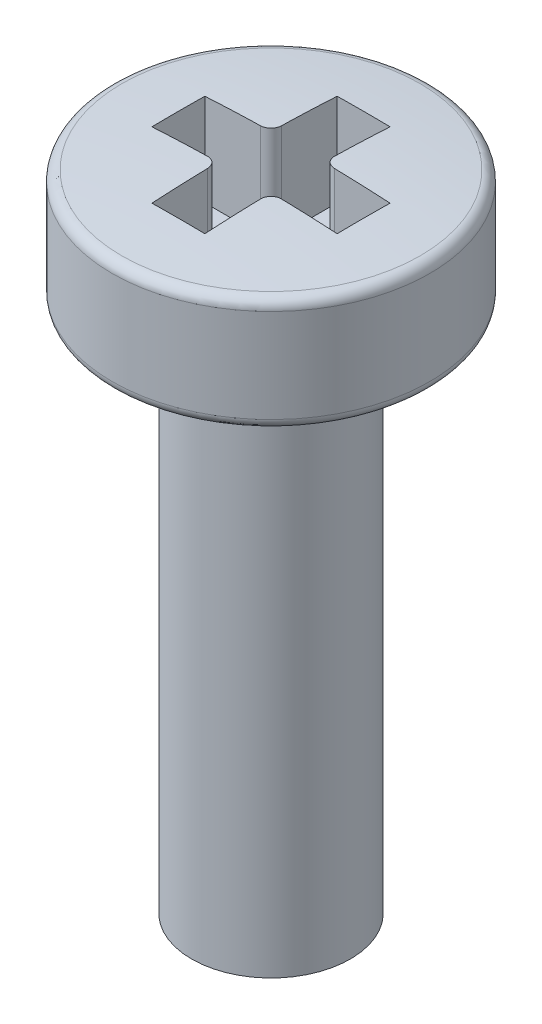
SolidWorks part; units mm, degrees
ref_plane "Alzado" through (0, 0, 0) normal (0, 0, 1) x (1, 0, 0)
ref_plane "Planta" through (0, 0, 0) normal (0, 1, 0) x (1, 0, 0)
ref_plane "Vista lateral" through (0, 0, 0) normal (1, 0, 0) x (0, 0, -1)
sketch "Croquis1" plane through (0, 0, 0) normal (0, 1, 0) x (1, 0, 0)
  circle A0 centre (0, 0) radius 1.5
  dimension "D1" = 3
extrude "Saliente-Extruir1" add sketch "Croquis1" along normal blind 10 contours A0
cosmetic thread "Cosmetic Thread1" parameters "D2"=2.439
ref_plane "Plano1" through (0, 13, 0) normal (0, 1, 0) x (1, 0, 0)
sketch "Croquis4" plane through (0, 0, 0) normal (0, 0, 1) x (1, 0, 0)
  line L0 (1.5, 10) -> (-1.5, 10) construction
  line L1 (0, 10) -> (2.8, 10)
  line L2 (0, 10) -> (0, 12.3)
  line L3 (-1.3027, 12.3) -> (0, 12.3) construction
  line L4 (3, 10.2) -> (3, 11.9682)
  arc A0 (2.8188, 12.1673) -> (0, 12.3) centre (0, -17.7) ccw
  arc A1 (2.8188, 12.1673) -> (3, 11.9682) centre (2.8, 11.9682) cw
  arc A2 (2.8, 10) -> (3, 10.2) centre (2.8, 10.2) ccw
  point P12 (3, 10)
  dimension "D2" = 0.2
  dimension "D4" = 30
  dimension "D1" = 3
  dimension "D3" = 2.3
revolve "Revolución1" add sketch "Croquis4" angle 360 about L2
sketch "Croquis5" plane through (0, 13, 0) normal (0, 1, 0) x (1, 0, 0)
  line L0 (-0.5, -0.7) -> (-0.5, -1.75)
  line L1 (-0.5, 1.75) -> (0.5, 1.75)
  line L2 (-0.5, 1.75) -> (-0.5, 0.7)
  line L3 (-0.5, -1.75) -> (0.5, -1.75)
  line L4 (0.5, 1.75) -> (0.5, 0.7)
  line L5 (1.75, 0.5) -> (0.7, 0.5)
  line L6 (1.75, 0.5) -> (1.75, -0.5)
  line L7 (1.75, -0.5) -> (0.7, -0.5)
  line L8 (-1.75, 0.5) -> (-1.75, -0.5)
  line L9 (-0.7, 0.5) -> (-1.75, 0.5)
  line L10 (0.5, -0.7) -> (0.5, -1.75)
  line L11 (-0.7, -0.5) -> (-1.75, -0.5)
  line L12 (-1.75, 0) -> (1.75, 0) construction
  line L13 (0, 1.75) -> (0, -1.75) construction
  arc A0 (-0.5, -0.7) -> (-0.7, -0.5) centre (-0.7, -0.7) ccw
  arc A1 (0.5, -0.7) -> (0.7, -0.5) centre (0.7, -0.7) cw
  arc A2 (0.7, 0.5) -> (0.5, 0.7) centre (0.7, 0.7) cw
  arc A3 (-0.5, 0.7) -> (-0.7, 0.5) centre (-0.7, 0.7) cw
  point P19 (-0.5, -0.5)
  point P26 (-0.5, 0.5)
  dimension "D2" = 0.2
  dimension "D1" = 1
  dimension "D3" = 3.5
extrude "Cortar-Extruir1" cut sketch "Croquis5" against normal blind 2.5
